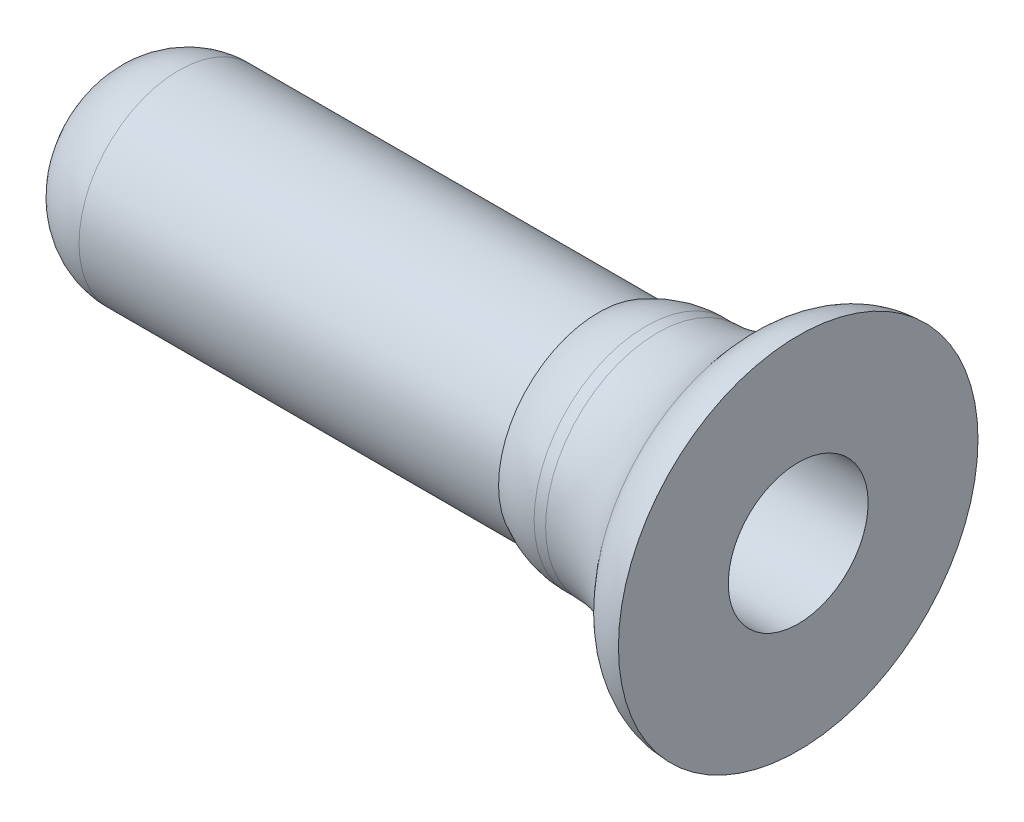
SolidWorks part; units mm, degrees
ref_plane "Front Plane" through (0, 0, 0) normal (0, 0, 1) x (1, 0, 0)
ref_plane "Top Plane" through (0, 0, 0) normal (0, 1, 0) x (1, 0, 0)
ref_plane "Right Plane" through (0, 0, 0) normal (1, 0, 0) x (0, 0, -1)
sketch "Sketch1" plane through (0, 0, 0) normal (0, 1, 0) x (1, 0, 0)
  line L0 (0, 0) -> (0, 9)
  line L1 (0, 9) -> (-3, 9)
  line L2 (-3, 9) -> (-3, 5.6054)
  line L3 (-3, 5.6054) -> (-10, 5.6054)
  line L4 (-10, 5.6054) -> (-10, 5)
  line L5 (-10, 5) -> (-35, 5)
  line L6 (-35, 5) -> (-35, 0)
  line L7 (-35, 0) -> (0, 0)
  dimension "D1" = 9
  dimension "D2" = 3
  dimension "D3" = 25
  dimension "2.5" = 7
  dimension "D4" = 5
revolve "Revolve1" add sketch "Sketch1" angle 360 about L7
sketch "Sketch2" plane through (0, 0, 0) normal (1, 0, 0) x (0, 0, -1)
  circle A0 centre (0, 0) radius 3.5
  dimension "D1" = 7
extrude "Cut-Extrude1" cut sketch "Sketch2" against normal blind 10
fillet "Fillet7" radius 3 1 edges at (-3, 0, 9)
fillet "Fillet8" radius 6 1 edges at (-3, 0, 5.6054)
fillet "Fillet9" radius 5 1 edges at (-10, 0, 5.6054)
fillet "Fillet10" radius 4 1 edges at (-35, 0, 5)
